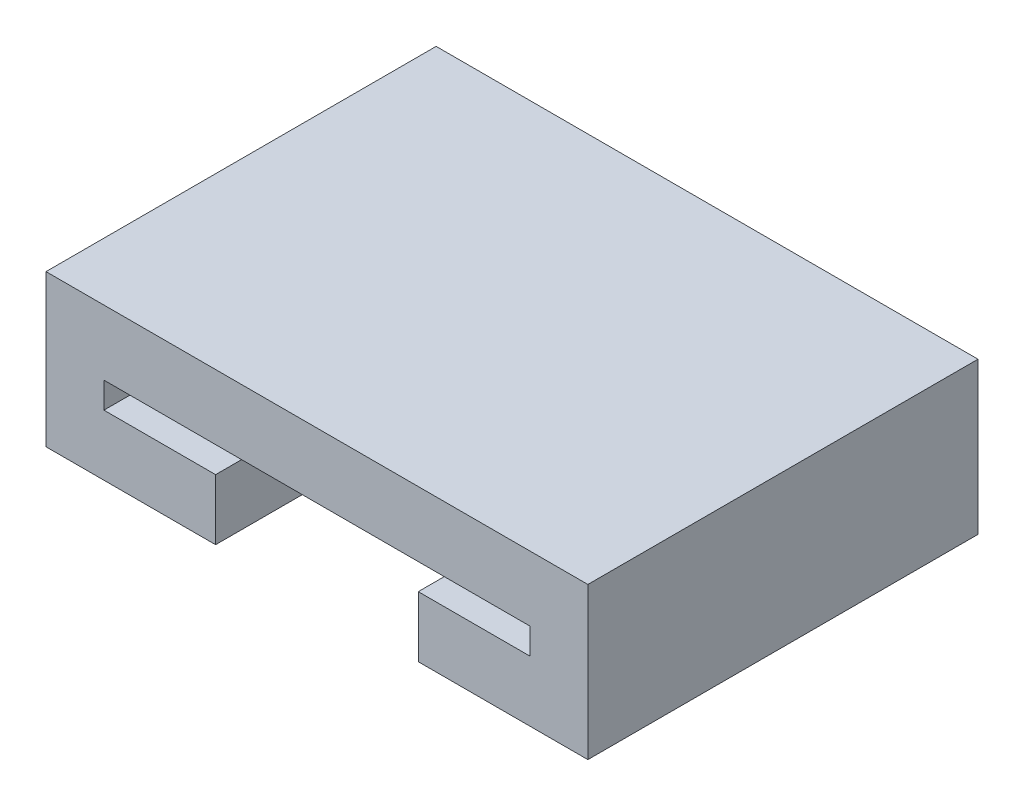
SolidWorks part; units mm, degrees
ref_plane "Front Plane" through (0, 0, 0) normal (0, 0, 1) x (1, 0, 0)
ref_plane "Top Plane" through (0, 0, 0) normal (0, 1, 0) x (1, 0, 0)
ref_plane "Right Plane" through (0, 0, 0) normal (1, 0, 0) x (0, 0, -1)
sketch "Sketch1" plane through (0, 0, 0) normal (0, 1, 0) x (1, 0, 0)
  line L1 (-12.5, -9) -> (12.5, -9)
  line L2 (-12.5, -9) -> (-12.5, 9)
  line L3 (-12.5, 9) -> (12.5, 9)
  line L4 (12.5, -9) -> (12.5, 9)
  line L5 (-12.5, -9) -> (12.5, 9) construction
  line L6 (-12.5, 9) -> (12.5, -9) construction
  point P0 (0, 0)
  dimension "D1" = 18
  dimension "D2" = 25
extrude "Boss-Extrude1" add sketch "Sketch1" along normal blind 7
sketch "Sketch2" plane through (0, 0, 9) normal (0, 0, 1) x (1, 0, 0)
  line L0 (-9.8273, 0) -> (9.8273, 0)
  line L1 (-12.5, 0) -> (12.5, 0) construction
  line L2 (9.8273, 0) -> (9.8273, 4)
  line L3 (9.8273, 4) -> (-9.8273, 4)
  line L4 (-9.8273, 4) -> (-9.8273, 0)
  line L5 (-9.8273, 2.8) -> (9.8273, 2.8)
  line L6 (-4.675, 2.8) -> (-4.675, 0)
  line L7 (0, 0) -> (0, 7) construction
  line L8 (-12.5, 7) -> (12.5, 7) construction
  line L9 (4.675, 2.8) -> (4.675, 0)
  line L10 (-0.425, 0) -> (-0.425, 5)
  line L11 (-0.425, 5) -> (0.425, 5)
  line L12 (0.425, 5) -> (0.425, 0)
  line L13 (0.725, 2.8) -> (0.725, 0)
  line L14 (-0.725, 2.8) -> (-0.725, 0)
  point P6 (0, 0)
  dimension "D1" = 4
  dimension "D2" = 1.2
  dimension "D3" = 9.35
  dimension "D4" = 0.85
  dimension "D5" = 0.3
extrude "Cut-Extrude1" cut sketch "Sketch2" against normal blind 13.5 contours L5 L10 L3 L4 | L3 L12 L5 L2 | L14 L5 L6 L0 | L5 L13 L4 L9 | L7 L0 L12 L5 | L4 L7 L5 L10 | L5 L7 L3 L10 | L7 L5 L12 L3 region at (-2.7, 1.4, 9) region at (-5.1262, 3.4, 9) region at (-0.2125, 1.4, 9) region at (-0.2125, 3.4, 9) region at (0.2125, 1.4, 9) region at (0.2125, 3.4, 9) region at (5.1262, 3.4, 9) region at (2.7, 1.4, 9)
sketch "Sketch8" plane through (0, 0, 9) normal (0, 0, 1) x (1, 0, 0)
  line L0 (-0.725, 2.8) -> (-0.425, 2.8)
  line L1 (-0.425, 2.8) -> (-0.425, 0)
  line L2 (-0.425, 0) -> (-0.725, 0)
  line L3 (-0.725, 0) -> (-0.725, 2.8)
  line L4 (0.425, 2.8) -> (0.725, 2.8)
  line L5 (0.725, 2.8) -> (0.725, 0)
  line L6 (0.725, 0) -> (0.425, 0)
  line L7 (0.425, 0) -> (0.425, 2.8)
extrude "Cut-Extrude4" cut sketch "Sketch8" against normal blind 10
